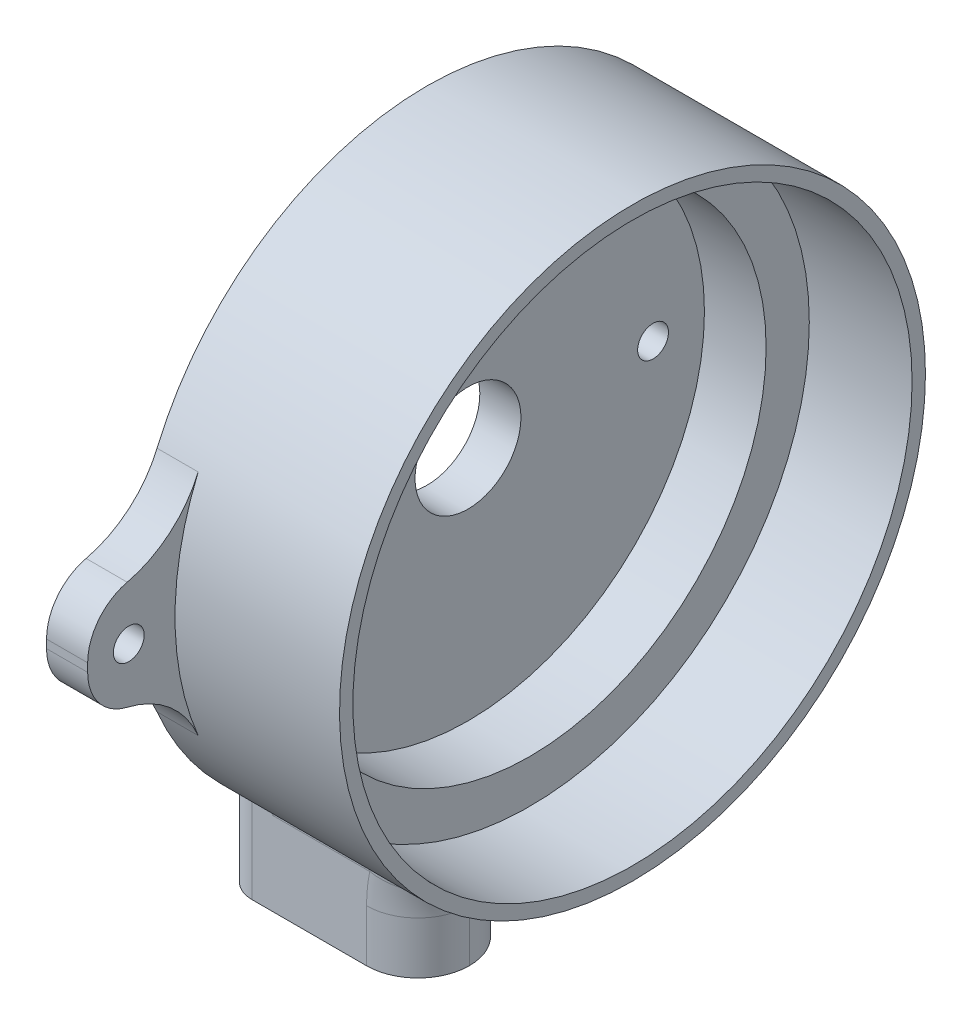
SolidWorks part; units mm, degrees
ref_plane "前视基准面" through (0, 0, 0) normal (0, 0, 1) x (1, 0, 0)
ref_plane "上视基准面" through (0, 0, 0) normal (0, 1, 0) x (1, 0, 0)
ref_plane "右视基准面" through (0, 0, 0) normal (1, 0, 0) x (0, 0, -1)
other "Configuration Table"
sketch "草图1" plane through (0, 0, 0) normal (1, 0, 0) x (0, 0, -1)
  circle A0 centre (0, 0) radius 28.5
  dimension "D1" = 57
extrude "凸台-拉伸1" add sketch "草图1" along normal blind 20
sketch "草图5" plane through (0, 0, 0) normal (-1, 0, 0) x (0, 0, 1)
  line L0 (0, 0) -> (0, 10.6758) construction
  line L1 (0, 0) -> (14.1218, 0) construction
  line L2 (0, 5.0001) -> (37, 5.0001)
  line L3 (-37, 5.0001) -> (0, 5.0001)
  line L4 (-37, 5.0001) -> (-37, -4.9999)
  line L5 (-37, -4.9999) -> (0, -4.9999)
  line L7 (37, 5.0001) -> (37, -4.9999)
  line L8 (37, -4.9999) -> (0, -4.9999)
  dimension "D1" = 37
  dimension "D2" = 10
  dimension "D3" = 5.0001
  dimension "D4" = 37
extrude "凸台-拉伸2" add sketch "草图5" against normal blind 4
sketch "草图2" plane through (20, 0, 0) normal (1, 0, 0) x (0, 0, -1)
  circle A0 centre (0, 0) radius 27.2
  dimension "D1" = 54.4
extrude "切除-拉伸1" cut sketch "草图2" against normal blind 10
sketch "草图3" plane through (10, 0, 0) normal (1, 0, 0) x (0, 0, -1)
  circle A0 centre (0, 0) radius 5.15
  dimension "D1" = 10.3
extrude "切除-拉伸2" cut sketch "草图3" against normal up to next
sketch "草图4" plane through (10, 0, 0) normal (1, 0, 0) x (0, 0, -1)
  circle A0 centre (0, 0) radius 23
  dimension "D1" = 46
extrude "切除-拉伸3" cut sketch "草图4" against normal blind 6
sketch "草图6" plane through (4, 0, 0) normal (1, 0, 0) x (0, 0, -1)
  line L0 (-37, 0.0001) -> (37, 0.0001) construction
  line L1 (-37, -4.9999) -> (-37, 5.0001) construction
  line L2 (37, 5.0001) -> (37, -4.9999) construction
  circle A0 centre (-33, 0.0001) radius 1.5
  circle A1 centre (33, 0.0001) radius 1.5
  dimension "D1" = 3
  dimension "D2" = 3
  dimension "D3" = 4
  dimension "D4" = 4
extrude "切除-拉伸4" cut sketch "草图6" against normal up to next
fillet "圆角1" radius 10 4 edges at (2, 5.0001, -28.058) (2, -4.9999, -28.058) (2, 5.0001, 28.058) (2, -4.9999, 28.058)
fillet "圆角2" radius 5 4 edges at (2, 5.0001, 37) (2, -4.9999, 37) (2, -4.9999, -37) (2, 5.0001, -37)
sketch "草图7" plane through (4, 0, 0) normal (1, 0, 0) x (0, 0, -1)
  line L0 (0, 0) -> (17.2688, 0) construction
  line L1 (0, 0) -> (-19.7613, 0) construction
  circle A1 centre (-18, 0) radius 1.5
  circle A2 centre (18, 0) radius 1.5
  dimension "D1" = 3
  dimension "D2" = 3
  dimension "D3" = 18
  dimension "D4" = 18
extrude "切除-拉伸5" cut sketch "草图7" against normal up to next
sketch "草图8" plane through (0, 0, 0) normal (-1, 0, 0) x (0, 0, 1)
  line L0 (0, 28.5) -> (0, -28.5) construction
  line L6 (-5, -23.058) -> (5, -23.058)
  line L7 (-5, -23.058) -> (-5, -28.058)
  line L8 (-5, -28.058) -> (5, -28.058)
  line L9 (5, -23.058) -> (5, -28.058)
  arc A0 (26.2479, 11.104) -> (-26.2479, 11.104) centre (0, 0) ccw construction
  arc A1 (-26.2479, -11.1038) -> (26.2479, -11.1038) centre (0, 0) ccw construction
  point P12 (-8.9067, -27.0725)
  dimension "D1" = 10
  dimension "D2" = 5
extrude "凸台-拉伸3" add sketch "草图8" along normal blind 15
fillet "圆角7" radius 10 3 edges at (0, -25.558, 5) (0, -23.058, 0) (0, -25.558, -5)
sketch "草图10" plane through (0, -28.058, 0) normal (0, -1, 0) x (-1, 0, 0)
  line L1 (15, -5) -> (-4.1294, -5)
  line L2 (15, -5) -> (15, 5)
  line L3 (15, 5) -> (-4.1294, 5)
  line L4 (-4.1294, -5) -> (-4.1294, 5)
  point P5 (15, 5)
extrude "凸台-拉伸4" add sketch "草图10" along normal blind 15.5 and the other way blind 1
sketch "草图9" plane through (0, -28.058, 0) normal (0, -1, 0) x (-1, 0, 0)
  line L0 (15, 0) -> (1.3687, 0) construction
  line L2 (15, -5) -> (15, 5) construction
  circle A0 centre (9, 0) radius 3
  dimension "D1" = 6
  dimension "D2" = 6
extrude "切除-拉伸6" cut sketch "草图9" along normal up to next and the other way blind 14.5
fillet "圆角9" radius 10 3 edges at (4.1294, -28.5, 0) (-2.9353, -28.058, 5) (-2.9353, -28.058, -5)
fillet "圆角10" radius 3 2 edges at (-15, -33.308, 5) (-15, -33.308, -5)
fillet "圆角11" radius 5 6 edges at (8.1128, -29.7472, -6.7908) (8.1128, -29.7472, 6.7908) (4.1294, -40.866, -5) (4.1294, -40.866, 5)
